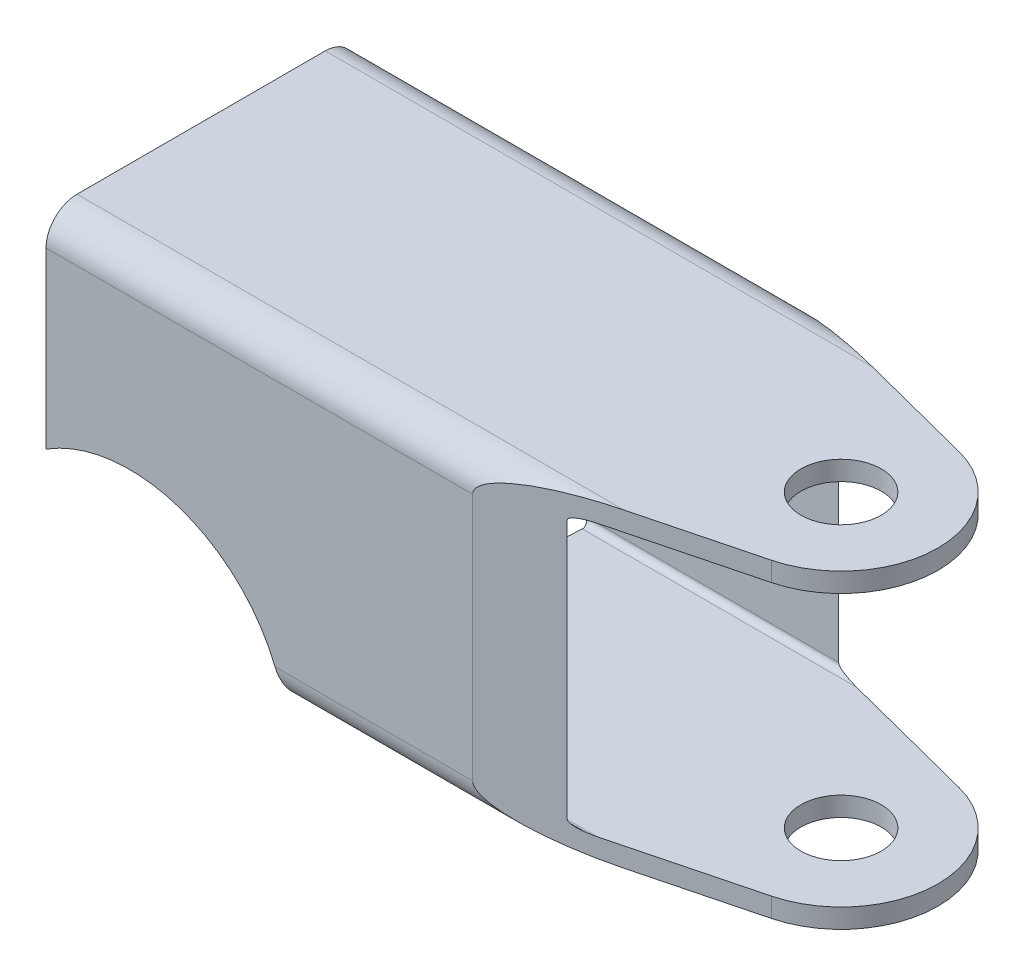
SolidWorks part; units mm, degrees
note: '?' marks a value the reader was unsure of.
ref_plane "Front Plane" through (0, 0, 0) normal (0, 0, 1) x (1, 0, 0)
ref_plane "Top Plane" through (0, 0, 0) normal (0, 1, 0) x (1, 0, 0)
ref_plane "Right Plane" through (0, 0, 0) normal (1, 0, 0) x (0, 0, -1)
sketch "Sketch1" plane through (0, 0, 0) normal (1, 0, 0) x (0, 0, -1)
  line L1 (-10.16, 12.7) -> (10.16, 12.7)
  line L2 (-12.7, 10.16) -> (-12.7, -10.16)
  line L3 (-10.16, -12.7) -> (10.16, -12.7)
  line L4 (12.7, 10.16) -> (12.7, -10.16)
  arc A0 (-10.16, 12.7) -> (-12.7, 10.16) centre (-10.16, 10.16) ccw
  arc A1 (-10.16, -12.7) -> (-12.7, -10.16) centre (-10.16, -10.16) cw
  arc A2 (10.16, 12.7) -> (12.7, 10.16) centre (10.16, 10.16) cw
  arc A3 (12.7, -10.16) -> (10.16, -12.7) centre (10.16, -10.16) cw
  point P4 (0, -12.7)
  point P7 (0, 0)
  point P15 (12.7, 0)
  dimension "D3" = 2.54
  dimension "D4" = 2.54
  dimension "D5" = 2.54
  dimension "D6" = 2.54
  dimension "D1" = 25.4
  dimension "D2" = 20.32
extrude "Boss-Extrude1" add sketch "Sketch1" along normal blind 25.4 and the other way blind 34.925
sketch "Sketch11" plane through (25.4, 0, 0) normal (1, 0, 0) x (0, 0, -1)
  line L0 (-10.16, -12.7) -> (10.16, -12.7) construction
  line L1 (-10.6045, 11.1125) -> (10.6045, 11.1125)
  line L2 (-11.1125, 10.6045) -> (-11.1125, -10.6045)
  line L3 (-10.6045, -11.1125) -> (10.6045, -11.1125)
  line L4 (11.1125, 10.6045) -> (11.1125, -10.6045)
  line L5 (10.16, 12.7) -> (-10.16, 12.7) construction
  line L6 (12.7, -10.16) -> (12.7, 10.16) construction
  line L7 (-12.7, 10.16) -> (-12.7, -10.16) construction
  arc A0 (10.6045, 11.1125) -> (11.1125, 10.6045) centre (10.6045, 10.6045) cw
  arc A1 (10.6045, -11.1125) -> (11.1125, -10.6045) centre (10.6045, -10.6045) ccw
  arc A2 (-11.1125, -10.6045) -> (-10.6045, -11.1125) centre (-10.6045, -10.6045) ccw
  arc A3 (-10.6045, 11.1125) -> (-11.1125, 10.6045) centre (-10.6045, 10.6045) ccw
  dimension "D1" = 1.5875
  dimension "D2" = 1.5875
  dimension "D3" = 1.5875
  dimension "D4" = 1.5875
  dimension "D5" = 0.508
extrude "Cut-Extrude4" cut sketch "Sketch11" against normal through all
sketch "Sketch12" plane through (0, 12.7, 0) normal (0, 1, 0) x (1, 0, 0)
  line L1 (0, 12.7) -> (50.8, 12.7)
  line L2 (50.8, 12.7) -> (50.8, -12.7)
  line L12 (50.8, -12.7) -> (0, -12.7)
  line L13 (19.4444, -7.6861) -> (0, -12.7)
  line L14 (19.4444, 7.6861) -> (0, 12.7)
  line L15 (-34.925, -12.7) -> (25.4, -12.7) construction
  line L16 (-34.925, 12.7) -> (25.4, 12.7) construction
  line L18 (25.4, 10.16) -> (25.4, -10.16) construction
  arc A1 (19.4444, -7.6861) -> (19.4444, 7.6861) centre (17.4625, 0) ccw
  point P8 (18.1688, 9.2165)
  dimension "D2" = 50.8
  dimension "D1" = 17.4625
extrude "Cut-Extrude5" cut sketch "Sketch12" against normal through all
sketch "Sketch14" plane through (0, 12.7, 0) normal (0, 1, 0) x (1, 0, 0)
  circle A0 centre (17.4625, 0) radius 3.2893
  arc A2 (19.4444, -7.6861) -> (19.4444, 7.6861) centre (17.4625, 0) ccw construction
  point P0 (17.4625, 0)
  point P6 (25.4, 0)
  dimension "D2" = 6.5786
  dimension "D1" = 7.9375
  dimension "D3" = 17.4625
extrude "Cut-Extrude6" cut sketch "Sketch14" against normal through all
ref_axis "Axis1" through (-23.6327, -18.2968, -33.7381) along (-0.0934, 0.0736, 0.9929)?
ref_point "Point2"
ref_plane "Plane1" through (-28.0006, -14.8562, 12.7) normal (-0.0934, 0.0736, 0.9929) x (0.9956, 0.0069, 0.0931)
sketch "Sketch15" plane through (-28.0006, -14.8562, 12.7) normal (-0.0934, 0.0736, 0.9929) x (0.9956, 0.0069, 0.0931)
  circle A0 centre (0, 0) radius 12.7
  dimension "D1" = 25.4
extrude "Cut-Extrude7" cut sketch "Sketch15" against normal blind 38.1 and the other way blind 12.7
